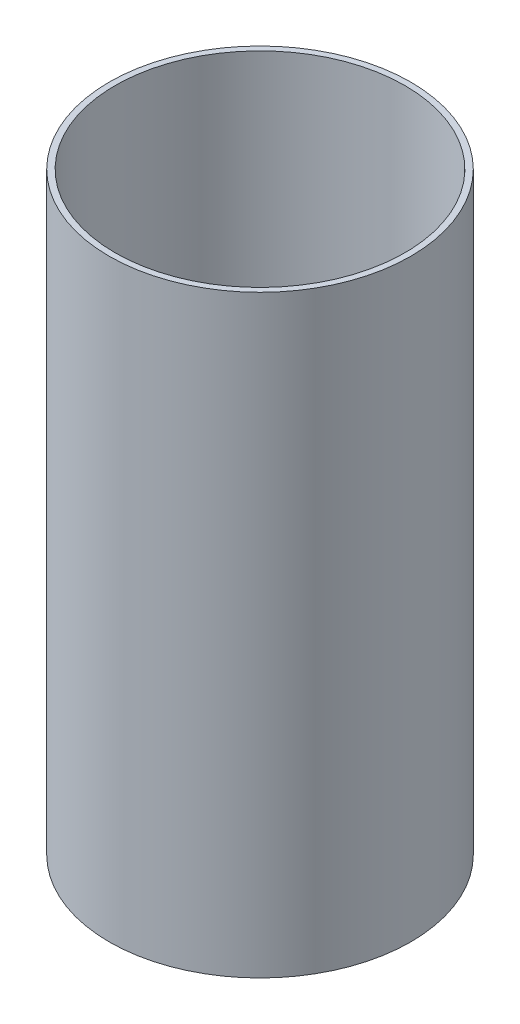
SolidWorks part; units mm, degrees
ref_plane "Front Plane" through (0, 0, 0) normal (0, 0, 1) x (1, 0, 0)
ref_plane "Top Plane" through (0, 0, 0) normal (0, 1, 0) x (1, 0, 0)
ref_plane "Right Plane" through (0, 0, 0) normal (1, 0, 0) x (0, 0, -1)
sketch "Sketch1" plane through (0, 0, 0) normal (0, 1, 0) x (1, 0, 0)
  circle A0 centre (0, 0) radius 76.2
  circle A1 centre (0, 0) radius 73.2
  dimension "D1" = 152.4
  dimension "D2" = 3
extrude "Boss-Extrude1" add sketch "Sketch1" along normal blind 150 and the other way blind 150
